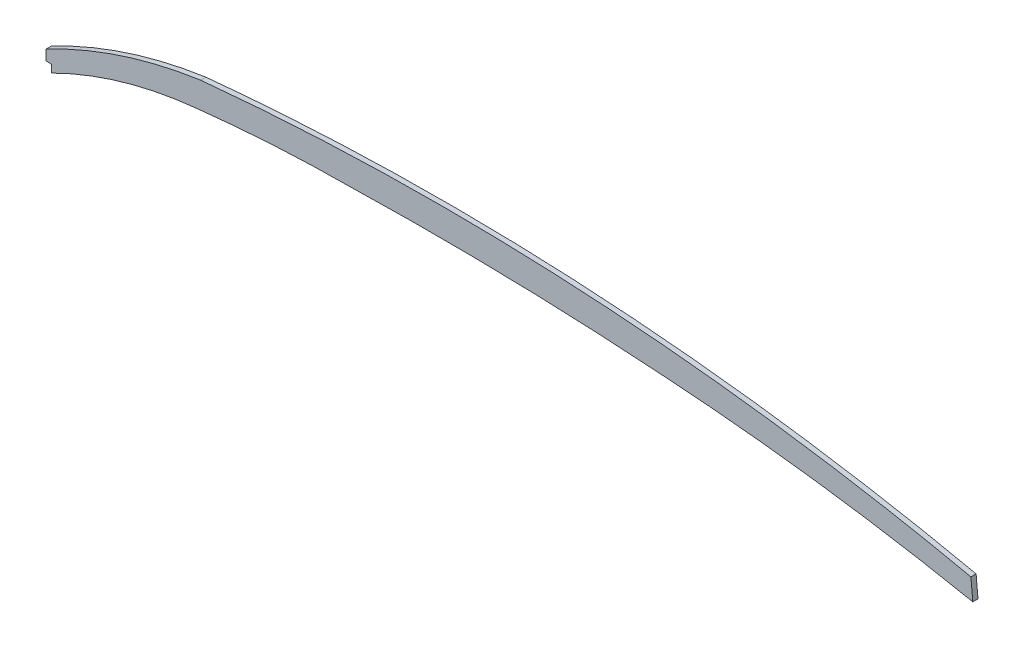
SolidWorks part; units mm, degrees
material "Balsa"
ref_plane "Front Plane" through (0, 0, 0) normal (0, 0, 1) x (1, 0, 0)
ref_plane "Top Plane" through (0, 0, 0) normal (0, 1, 0) x (1, 0, 0)
ref_plane "Right Plane" through (0, 0, 0) normal (1, 0, 0) x (0, 0, -1)
sketch "Sketch1" plane through (0, 0, 0) normal (0, 0, 1) x (1, 0, 0)
  line L0 (0, 85.9425) -> (0, 98.6503)
  line L1 (566.0852, 89.3165) -> (564.9321, 101.9675)
  arc A6 (0, 85.9425) -> (92.3925, 113.3646) centre (117.1549, -139.4255) cw
  arc A7 (92.3925, 113.3646) -> (185.8959, 118.7316) centre (190.0181, -770.2588) cw
  arc A8 (0, 98.6503) -> (94.4926, 129.4761) centre (136.5172, -159.585) cw
  arc A9 (185.8959, 118.7316) -> (373.1011, 114.6803) centre (236.8429, -1854.3326) cw
  arc A10 (373.1011, 114.6803) -> (566.0852, 89.3165) centre (283.2319, -1315.9598) cw
  spline S6 degree 3 poles (2840.1742, -3011.9753) (2207.2857, -1054.6085) (1410.1047, -9.0147) (438.4396, 123.9347) (428.6248, 125.1803) (408.999, 127.4768) (399.1847, 128.5284) (369.7378, 131.3944) (350.1011, 132.9205) (291.1746, 136.3531) (251.8686, 137.116) (-696.3591, 118.7734) (-1616.8272, -712.5738) (-2553.4552, -2680.6967) knots -5.888628 -5.888628 -5.888628 -5.888628 0.25 0.25 0.3125 0.3125 0.375 0.375 0.5 0.5 0.75 0.75 6.527741 6.527741 6.527741 6.527741 only from (564.9321, 101.9675) to (94.4926, 129.4761)
  spline S7 degree 3 poles (564.9321, 101.9675) (526.3055, 110.3591) (487.4057, 117.2349) (438.4396, 123.9347) (428.6248, 125.1803) (408.999, 127.4768) (399.1847, 128.5284) (369.7378, 131.3944) (350.1011, 132.9205) (291.1746, 136.3531) (251.8686, 137.116) (173.2133, 135.5945) (133.864, 133.3102) (94.4926, 129.4761) knots 0 0 0 0 0.25 0.25 0.3125 0.3125 0.375 0.375 0.5 0.5 0.75 0.75 1 1 1 1
  dimension "D4" = 92.3925
  dimension "D2" = 254
  dimension "D8" = 187.2051
  dimension "D9" = 28.7378
  dimension "D1" = 292.1
  dimension "D3" = 889
  dimension "D10" = 1973.7219
  dimension "D11" = 1433.46
  dimension "D5" = 27.4221
  dimension "D6" = 93.5034
  dimension "D7" = 32.7892
extrude "Boss-Extrude1" add sketch "Sketch1" against normal mid plane 3.175 contours L1 S7 A8 L0 A6 A7 A9 A10 region at (279.3924, 119.3666, 0)
sketch "Sketch2" plane through (0, 0, 1.5875) normal (0, 0, 1) x (1, 0, 0)
  line L0 (0, 0.1991) -> (0, 85.9425) construction
  line L1 (0, 49.7106) -> (0, -49.3123) construction
  line L3 (0, 85.9425) -> (3.3528, 85.9425)
  line L4 (0, 85.9425) -> (0, 92.3687)
  line L5 (0, 92.3687) -> (3.3528, 92.3687)
  line L6 (3.3528, 85.9425) -> (3.3528, 92.3687)
  dimension "D1" = 85.7434
  dimension "D2" = 6.4262
  dimension "D3" = 3.3528
extrude "Cut-Extrude1" cut sketch "Sketch2" against normal through all
equation "\"slotwidth\"=0.167708"
